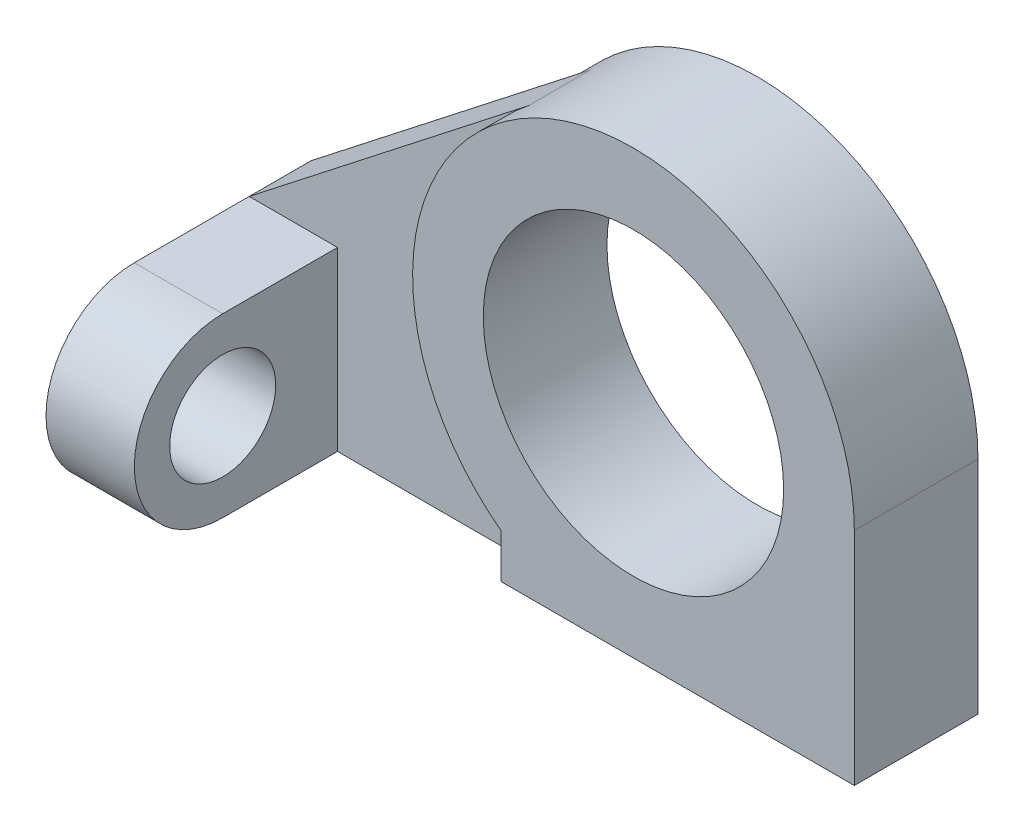
SolidWorks part; units mm, degrees
ref_plane "Ön Düzlem" through (0, 0, 0) normal (0, 0, 1) x (1, 0, 0)
ref_plane "Üst Düzlem" through (0, 0, 0) normal (0, 1, 0) x (1, 0, 0)
ref_plane "Sağ Düzlem" through (0, 0, 0) normal (1, 0, 0) x (0, 0, -1)
sketch "Çizim1" plane through (0, 0, 0) normal (0, 0, 1) x (1, 0, 0)
  line L0 (0, 0) -> (0, 5)
  line L1 (0, 0) -> (40, 0)
  line L2 (40, 0) -> (40, 25)
  line L3 (15, 25) -> (15, -17.0888) construction
  circle A0 centre (15, 25) radius 25
  circle A1 centre (15, 25) radius 17
  dimension "D3" = 34
  dimension "D4" = 50
  dimension "D1" = 40
  dimension "D2" = 25
  dimension "D5" = 15
extrude "Yükseklik-Ekstrüzyon1" add sketch "Çizim1" along normal blind 14 contours A1 A0 region at (4.1359, 46.7282, 0)
extrude "Yükseklik-Ekstrüzyon2" add sketch "Çizim1<3>" along normal blind 14 contours A0 L0 L1 | A0 L1 L2 region at (3.6709, 1.4702, 0) region at (34.4158, 5.5842, 0)
sketch "Çizim1<3>" plane through (0, 0, 0) normal (0, 0, 1) x (1, 0, 0) same geometry as "Çizim1"
ref_plane "Düzlem1" through (-32, 0, 0) normal (1, 0, 0) x (0, 0, -1)
sketch "Çizim2" plane through (-32, 0, 0) normal (1, 0, 0) x (0, 0, -1)
  line L0 (-14, 0) -> (0, 0) construction
  line L1 (-3.5, 0) -> (-10.5, 0)
  line L2 (-3.5, 0) -> (-3.5, 16)
  line L3 (-3.5, 16) -> (-10.5, 16)
  line L4 (-10.5, 0) -> (-10.5, 16)
  line L5 (-3.5, 16) -> (-3.5, 20)
  line L6 (-3.5, 20) -> (-23.5, 20)
  line L7 (-23.5, 16) -> (-23.5, 10) construction
  line L8 (-3.5, 20) -> (-3.5, 16)
  line L9 (-10.5, 0) -> (-23.5, 0)
  circle A0 centre (-23.5, 10) radius 6
  arc A1 (-23.5, 20) -> (-23.5, 0) centre (-23.5, 10) ccw
  dimension "D6" = 20
  dimension "D7" = 12
  dimension "D1" = 3.5
  dimension "D2" = 7
  dimension "D3" = 16
  dimension "D4" = 4
  dimension "D5" = 20
  dimension "D8" = 13
extrude "Yükseklik-Ekstrüzyon3" add sketch "Çizim2" along normal blind 4 separate body contours L4 L1 L2 L3 region at (-32, 8, 7)
extrude "Yükseklik-Ekstrüzyon4" add sketch "Çizim2<3>" along normal blind 10 contours L6 A1 L9 L4 L3 L5 A0 region at (-32, 0.3606, 17)
sketch "Çizim2<3>" plane through (-32, 0, 0) normal (1, 0, 0) x (0, 0, -1) same geometry as "Çizim2"
ref_plane "Düzlem2" through (0, 0, 7) normal (0, 0, 1) x (1, 0, 0)
sketch "Çizim3" plane through (0, 0, 7) normal (0, 0, 1) x (1, 0, 0)
  line L0 (-32, 20) -> (-0.3935, 44.6987)
  line L1 (-32, 20) -> (-22, 20)
  line L2 (-22, 20) -> (-32, 20) construction
  line L3 (-22, 20) -> (-22, 0)
  line L4 (-22, 0) -> (0, 0)
  line L5 (0, 0) -> (0, 5)
  arc A1 (40, 25) -> (0, 5) centre (15, 25) ccw construction
  arc A3 (0, 5) -> (-0.3935, 44.6987) centre (15, 25) cw
sketch "Çizim4" plane through (-32, 0, 0) normal (1, 0, 0) x (0, 0, -1)
  line L1 (-3.5, 0) -> (-10.5, 0)
  line L2 (-3.5, 0) -> (-3.5, 16)
  line L3 (-3.5, 16) -> (-10.5, 16)
  line L4 (-10.5, 0) -> (-10.5, 16)
  dimension "D1" = 16
  dimension "D2" = 7
extrude "Yükseklik-Ekstrüzyon11" add sketch "Çizim4" along normal blind 10 and the other way blind 4
extrude "Yükseklik-Ekstrüzyon12" add sketch "Çizim3" along normal mid plane 7
